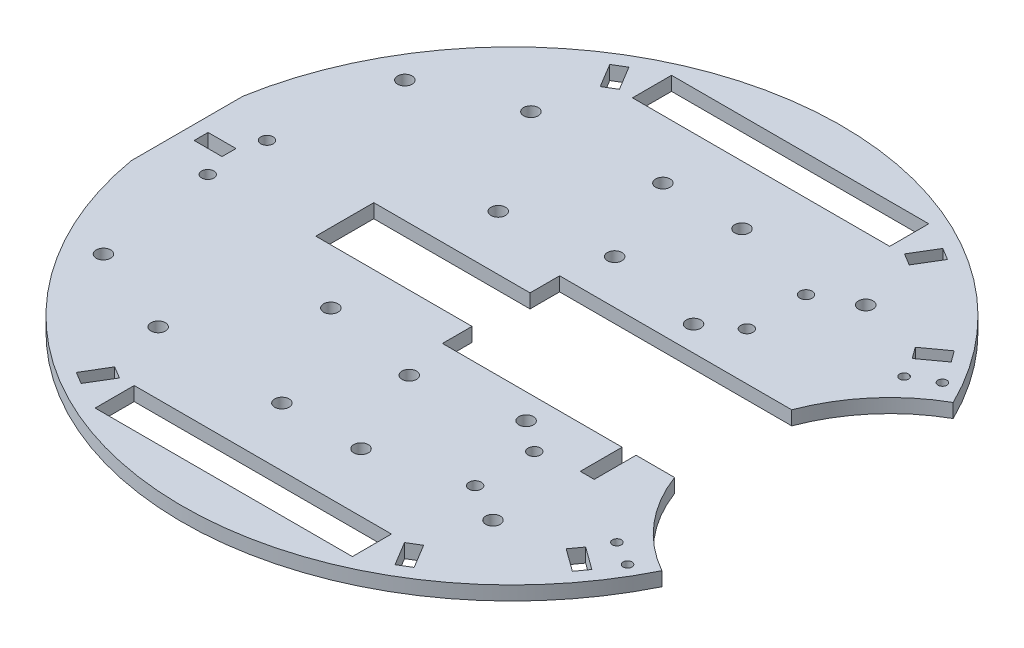
SolidWorks part; units mm, degrees
material "Acrylic (Medium-high impact)"
ref_plane "Front Plane" through (0, 0, 0) normal (0, 0, 1) x (1, 0, 0)
ref_plane "Top Plane" through (0, 0, 0) normal (0, 1, 0) x (1, 0, 0)
ref_plane "Right Plane" through (0, 0, 0) normal (1, 0, 0) x (0, 0, -1)
sketch "Sketch1" plane through (0, 0, 0) normal (0, 1, 0) x (1, 0, 0)
  line L0 (67.2709, 33.1606) -> (86.0323, 0) construction
  line L1 (86.0323, 0) -> (67.2709, -33.1606) construction
  line L2 (0, 65.5895) -> (0, 75) construction
  line L3 (-29.2721, -56.6995) -> (29.2721, -56.6995)
  line L4 (-29.2721, -56.6995) -> (-29.2721, -65.5895)
  line L5 (-29.2721, -65.5895) -> (29.2721, -65.5895)
  line L6 (29.2721, -56.6995) -> (29.2721, -65.5895)
  line L7 (-29.2721, 65.5895) -> (29.2721, 65.5895)
  line L8 (-29.2721, 65.5895) -> (-29.2721, 56.6995)
  line L9 (-29.2721, 56.6995) -> (29.2721, 56.6995)
  line L10 (29.2721, 65.5895) -> (29.2721, 56.6995)
  line L11 (29.2721, 65.5895) -> (30.566, 68.4888) construction
  line L12 (29.2721, -65.5895) -> (30.566, -68.4888) construction
  line L13 (-62.4869, 6.731) -> (-62.4869, -6.731) construction
  line L14 (-62.4869, 0) -> (-73.9169, 0) construction
  line L15 (52.069, 39.728) -> (57.2092, 43.4563)
  line L16 (52.069, 39.728) -> (53.9332, 37.1579)
  line L17 (57.2092, 43.4563) -> (59.0734, 40.8862)
  line L18 (53.9332, 37.1579) -> (59.0734, 40.8862)
  line L19 (52.069, 39.728) -> (59.0734, 40.8862) construction
  line L20 (57.2092, 43.4563) -> (53.9332, 37.1579) construction
  line L21 (58.1413, 42.1713) -> (60.7114, 44.0354) construction
  line L22 (60.7114, 44.0354) -> (67.2709, 33.1606) construction
  line L23 (0, 0) -> (86.0323, 0) construction
  line L24 (53.9332, -37.1579) -> (59.0734, -40.8862)
  line L25 (57.2092, -43.4563) -> (59.0734, -40.8862)
  line L26 (52.069, -39.728) -> (57.2092, -43.4563)
  line L27 (52.069, -39.728) -> (53.9332, -37.1579)
  line L28 (-38.1, -42.418) -> (0, -23.368) construction
  line L29 (0, -23.368) -> (38.1, -42.418) construction
  line L30 (-38.1, -42.418) -> (38.1, -42.418) construction
  line L31 (0, -23.368) -> (0, -42.418) construction
  line L32 (-2.4867, 6.604) -> (-2.4867, 13.335) construction
  line L33 (38.4073, -13.335) -> (-2.4867, -13.335) construction
  line L34 (-2.4867, -13.335) -> (-2.4867, -6.604) construction
  line L35 (-2.4867, 13.335) -> (38.4073, 13.335) construction
  line L36 (38.4073, 13.335) -> (41.5823, 13.335)
  line L37 (32.441, -56.8953) -> (35.7191, -62.3337)
  line L38 (32.441, -56.8953) -> (35.1602, -55.2563)
  line L39 (35.7191, -62.3337) -> (38.4383, -60.6947)
  line L40 (35.1602, -55.2563) -> (38.4383, -60.6947)
  line L41 (-58.6769, -34.29) -> (-58.6769, 34.29) construction
  line L42 (0, 0) -> (-16.51, 0) construction
  line L43 (-58.6769, 0) -> (-62.4869, 0) construction
  line L44 (41.5823, 13.335) -> (50.3421, 13.335)
  line L45 (41.5823, -13.335) -> (46.2813, -13.335)
  line L46 (-2.4867, -6.604) -> (-2.4867, -13.335)
  line L47 (-73.9169, 12.7) -> (-73.9169, -12.7)
  line L48 (38.4073, 13.335) -> (-2.4867, 13.335)
  line L49 (-2.4867, 13.335) -> (-2.4867, 6.604)
  line L50 (-2.4867, -13.335) -> (38.4073, -13.335)
  line L51 (46.2813, -13.335) -> (50.3421, -13.335)
  line L52 (-2.4867, 0) -> (-38.0467, 0) construction
  line L53 (-2.4867, 6.604) -> (-38.0467, 6.604)
  line L54 (14.856, 13.335) -> (14.856, 0) construction
  line L55 (-2.4867, -6.604) -> (-38.0467, -6.604)
  line L56 (-38.0467, 6.604) -> (-38.0467, -6.604)
  line L57 (14.856, 0) -> (14.856, -13.335) construction
  line L58 (32.441, -56.8953) -> (38.4383, -60.6947) construction
  line L59 (35.7191, -62.3337) -> (35.1602, -55.2563) construction
  line L60 (41.5823, -13.335) -> (41.5823, -22.86)
  line L61 (41.5823, -22.86) -> (38.4073, -22.86)
  line L62 (38.4073, -13.335) -> (38.4073, -22.86)
  line L63 (33.8006, -56.0758) -> (0, 0) construction
  line L64 (37.0787, -61.5142) -> (38.7178, -64.2334) construction
  line L65 (-32.441, -56.8953) -> (-35.1602, -55.2563)
  line L66 (-32.441, -56.8953) -> (-35.7191, -62.3337)
  line L67 (-35.7191, -62.3337) -> (-38.4383, -60.6947)
  line L68 (-35.1602, -55.2563) -> (-38.4383, -60.6947)
  line L69 (-35.1602, 55.2563) -> (-38.4383, 60.6947)
  line L70 (-32.441, 56.8953) -> (-35.1602, 55.2563)
  line L71 (-32.441, 56.8953) -> (-35.7191, 62.3337)
  line L72 (-35.7191, 62.3337) -> (-38.4383, 60.6947)
  line L73 (35.1602, 55.2563) -> (38.4383, 60.6947)
  line L74 (32.441, 56.8953) -> (35.1602, 55.2563)
  line L75 (32.441, 56.8953) -> (35.7191, 62.3337)
  line L76 (35.7191, 62.3337) -> (38.4383, 60.6947)
  line L77 (-73.9169, 0) -> (-70.7419, 0) construction
  line L78 (-70.7419, 1.5875) -> (-64.3919, 1.5875)
  line L79 (-70.7419, 1.5875) -> (-70.7419, -1.5875)
  line L80 (-70.7419, -1.5875) -> (-64.3919, -1.5875)
  line L81 (-64.3919, 1.5875) -> (-64.3919, -1.5875)
  arc A0 (67.2709, 33.1606) -> (-73.9169, 12.7) centre (0, 0) ccw
  arc A1 (67.2709, -33.1606) -> (55.0862, -22.225) centre (86.0323, 0) cw
  circle A2 centre (-62.4869, 6.731) radius 1.397
  circle A3 centre (-62.4869, -6.731) radius 1.397
  circle A4 centre (-38.1, -42.418) radius 1.651
  circle A5 centre (38.1, -42.418) radius 1.651
  circle A6 centre (38.1, 42.418) radius 1.651
  circle A7 centre (0, -23.368) radius 1.651
  circle A8 centre (-38.1, 42.418) radius 1.651
  circle A9 centre (0, 23.368) radius 1.651
  circle A10 centre (29.2721, -37.6495) radius 1.397
  arc A11 (55.0862, -22.225) -> (50.3421, -13.335) centre (86.0323, 0) cw
  circle A12 centre (-58.6769, 34.29) radius 1.651
  circle A13 centre (62.1411, -35.8306) radius 1.016
  circle A14 centre (56.5708, -32.6791) radius 1.016
  circle A15 centre (-58.6769, -34.29) radius 1.651
  arc A16 (50.3421, 13.335) -> (67.2709, 33.1606) centre (86.0323, 0) cw
  arc A17 (-73.9169, -12.7) -> (67.2709, -33.1606) centre (0, 0) ccw
  circle A18 centre (29.2721, -24.1875) radius 1.397
  circle A19 centre (29.2721, 37.6495) radius 1.397
  circle A20 centre (29.2721, 24.1875) radius 1.397
  circle A21 centre (8.9992, -43.3535) radius 1.651
  circle A22 centre (-9.0008, -43.3535) radius 1.651
  circle A23 centre (-9.0008, 43.3535) radius 1.651
  circle A24 centre (8.9992, 43.3535) radius 1.651
  circle A25 centre (62.1411, 35.8306) radius 1.016
  circle A26 centre (56.5708, 32.6791) radius 1.016
  circle A27 centre (56.5708, 32.6791) radius 1.016 construction
  circle A28 centre (22.2783, 19.05) radius 1.651
  circle A29 centre (22.2783, -19.05) radius 1.651
  circle A30 centre (-22.1717, -19.05) radius 1.651
  circle A31 centre (-22.1717, 19.05) radius 1.651
  circle A32 centre (22.2783, 19.05) radius 1.651 construction
  point P24 (55.5712, 40.3071)
  point P50 (41.5823, 0)
  point P56 (47.9323, 0)
  point P63 (35.4397, -58.795)
  dimension "D1" = 150
  dimension "D7" = 11.43
  dimension "D8" = 2.794
  dimension "D14" = 76.2
  dimension "D16" = 3.302
  dimension "D22" = 13.208
  dimension "D27" = 3.302
  dimension "D34" = 2.794
  dimension "D36" = 19.05
  dimension "D2" = 121
  dimension "D3" = 38.1
  dimension "D4" = 58.5441
  dimension "D5" = 8.89
  dimension "D6" = 3.175
  dimension "D9" = 13.462
  dimension "D10" = 6.35
  dimension "D11" = 3.175
  dimension "D12" = 3.175
  dimension "D13" = 12.7
  dimension "D15" = 3.175
  dimension "D17" = 42.418
  dimension "D18" = 25.4
  dimension "D19" = 26.67
  dimension "D20" = 44.069
  dimension "D21" = 17.3428
  dimension "D23" = 38.1
  dimension "D24" = 9.525
  dimension "D25" = 15.24
  dimension "D26" = 68.58
  dimension "D28" = 44.45
  dimension "D29" = 35.56
  dimension "D30" = 6.35
  dimension "D31" = 88.519
  dimension "D32" = 16.51
  dimension "D33" = 13.462
  dimension "D35" = 19.05
  dimension "D37" = 3.175
  dimension "D38" = 3.175
  dimension "D39" = 3.175
extrude "Boss-Extrude1" add sketch "Sketch1" along normal blind 3.175
equation "\"Diameter\"= 2.75"
equation "\"D4@Sketch1\"=\"Diameter\"*sin(arccos(1-(5/(4*\"Diameter\"))))"
